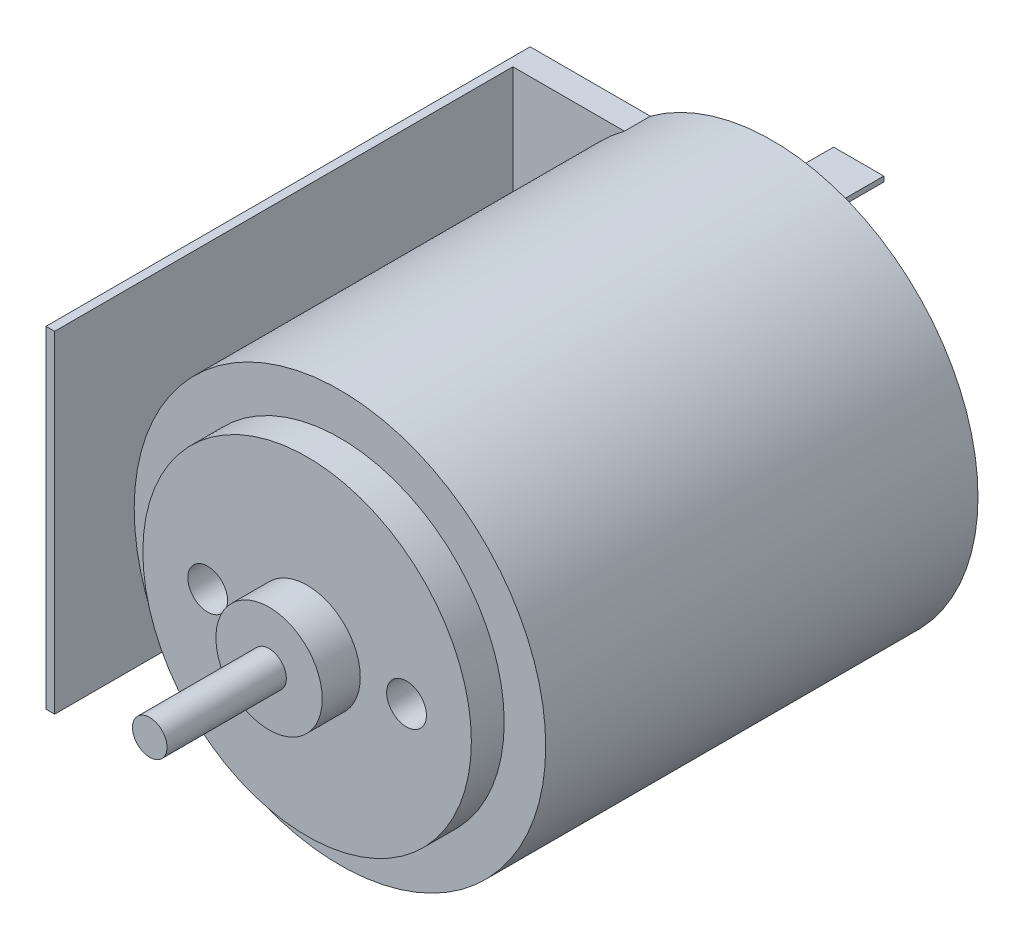
SolidWorks part; units mm, degrees
ref_plane "正面" through (0, 0, 0) normal (0, 0, 1) x (1, 0, 0)
ref_plane "平面" through (0, 0, 0) normal (0, 1, 0) x (1, 0, 0)
ref_plane "右側面" through (0, 0, 0) normal (1, 0, 0) x (0, 0, -1)
sketch "ｽｹｯﾁ2" plane through (0, 0, 0) normal (0, 0, 1) x (1, 0, 0)
  circle A0 centre (0, 0) radius 9.5
  circle A1 centre (0, 0) radius 11.9
  circle A2 centre (0, 0) radius 3.075
  circle A3 centre (0, 0) radius 1
  circle A4 centre (0, 0) radius 4.25
  dimension "D1" = 23.8
  dimension "D2" = 19
  dimension "D3" = 6.15
  dimension "D4" = 2
  dimension "D5" = 8.5
extrude "ﾎﾞｽ - 押し出し1" add sketch "ｽｹｯﾁ2" along normal blind 36 contours A3 region at (0, 0, 0)
extrude "ﾎﾞｽ - 押し出し2" add sketch "ｽｹｯﾁ2<4>" along normal blind 29.1 contours A2 A3 region at (-2.988, 0, 0)
sketch "ｽｹｯﾁ2<4>" plane through (0, 0, 0) normal (0, 0, 1) x (1, 0, 0) same geometry as "ｽｹｯﾁ2"
extrude "ﾎﾞｽ - 押し出し3" add sketch "ｽｹｯﾁ2<5>" along normal blind 26.9 and the other way blind 2 contours A4 A2 region at (-4.1298, 0, 0)
sketch "ｽｹｯﾁ2<5>" plane through (0, 0, 0) normal (0, 0, 1) x (1, 0, 0) same geometry as "ｽｹｯﾁ2"
extrude "ﾎﾞｽ - 押し出し4" add sketch "ｽｹｯﾁ2<6>" along normal blind 26.9 contours A0 A4 region at (-9.2313, 0, 0)
sketch "ｽｹｯﾁ2<6>" plane through (0, 0, 0) normal (0, 0, 1) x (1, 0, 0) same geometry as "ｽｹｯﾁ2"
extrude "ﾎﾞｽ - 押し出し5" add sketch "ｽｹｯﾁ2<7>" along normal blind 25 contours A1 A0 region at (-11.5634, 0, 0)
sketch "ｽｹｯﾁ2<7>" plane through (0, 0, 0) normal (0, 0, 1) x (1, 0, 0) same geometry as "ｽｹｯﾁ2"
ref_plane "平面1" through (0, 0, 26.9) normal (0, 0, 1) x (1, 0, 0)
ref_plane "平面2" through (0, 0, -10) normal (0, 0, -1) x (-1, 0, 0)
ref_plane "平面3" through (0, 0, 0) normal (0, 0, -1) x (-1, 0, 0)
sketch "ｽｹｯﾁ5" plane through (0, 0, 0) normal (0, 0, -1) x (-1, 0, 0)
  line L5 (1.45, -7.8068) -> (-1.45, -7.8068)
  line L6 (1.45, -7.8068) -> (1.45, -7.5068)
  line L11 (1.45, -7.5068) -> (-1.45, -7.5068)
  line L12 (-1.45, -7.8068) -> (-1.45, -7.5068)
  line L13 (1.45, -7.8068) -> (-1.45, -7.5068) construction
  line L14 (1.45, -7.5068) -> (-1.45, -7.8068) construction
  line L15 (-1.45, 8.3397) -> (1.45, 8.3397)
  line L16 (-1.45, 8.3397) -> (-1.45, 8.0397)
  line L17 (-1.45, 8.0397) -> (1.45, 8.0397)
  line L18 (1.45, 8.3397) -> (1.45, 8.0397)
  line L19 (-1.45, 8.3397) -> (1.45, 8.0397) construction
  line L20 (-1.45, 8.0397) -> (1.45, 8.3397) construction
  circle A0 centre (6.45, 0) radius 1
  circle A1 centre (-6.45, 0) radius 1
  point P4 (-0.6526, 8.1897)
  point P5 (0, 8.1897)
  point P6 (0, -7.6568)
  point P9 (1.8202, -7.6568)
  dimension "D3" = 2
  dimension "D4" = 2
  dimension "D1" = 6.45
  dimension "D2" = 6.45
  dimension "D5" = 2.9
  dimension "D6" = 0.3
  dimension "D7" = 2.9
  dimension "D8" = 0.3
extrude "ﾎﾞｽ - 押し出し6" add sketch "ｽｹｯﾁ5" along normal blind 5 contours L16 L15 L18 L17 | L6 L5 L12 L11
sketch "ｽｹｯﾁ6" plane through (0, 0, 0) normal (0, 0, -1) x (-1, 0, 0)
  circle A0 centre (6.45, 0) radius 1
  circle A1 centre (-6.45, 0) radius 1
  dimension "D1" = 6.45
  dimension "D2" = 6.45
hole_wizard "M2 ねじ穴2" positions "ｽｹｯﾁ9" profile "ｽｹｯﾁ10" tap size "M2" standard "IS"
sketch "ｽｹｯﾁ9" plane through (0, 0, 0) normal (0, 0, -1) x (-1, 0, 0)
  point P0 (-6.45, 0)
  point P3 (6.45, 0)
sketch "ｽｹｯﾁ10" plane through (6.45, 0, 0) normal (1, 0, 0) x (0, 1, 0)
  line L0 (0, 0) -> (0, 6.4807)
  line L1 (0, 6.4807) -> (0.8, 6)
  line L2 (0.8, 6) -> (0.8, 0)
  line L5 (0.8, 0) -> (0, 0)
  line L10 (0, 6.4807) -> (-0.8, 6) construction
  line L11 (0, -6.35) -> (0, 107.95) construction
  dimension "ねじ下穴ﾄﾞﾘﾙ直径" = 1.6
  dimension "ねじ下穴ﾄﾞﾘﾙの深さ" = 6
  dimension "ﾄﾞﾘﾙ角度" = 118
cosmetic thread "穴のねじ山2" parameters "D1"=4, "D2"=2
cosmetic thread "穴のねじ山3" parameters "D1"=4, "D2"=2
ref_plane "平面4" through (0, 0, 36.9) normal (0, 0, 1) x (1, 0, 0)
sketch "ｽｹｯﾁ14" plane through (0, 0, 26.9) normal (0, 0, 1) x (1, 0, 0)
  circle A0 centre (5.75, 0) radius 1.15
  circle A1 centre (-5.75, 0) radius 1.15
  dimension "D3" = 2.3
  dimension "D4" = 2.3
  dimension "D1" = 5.75
  dimension "D2" = 5.75
extrude "ｶｯﾄ - 押し出し1" cut sketch "ｽｹｯﾁ14" against normal blind 3
sketch "ｽｹｯﾁ15" plane through (0, 0, 0) normal (0, 0, -1) x (-1, 0, 0)
  line L1 (13.5, -9.589) -> (14, -9.589)
  line L2 (13.5, -9.589) -> (13.5, 9.589)
  line L3 (13.5, 9.589) -> (14, 9.589)
  line L4 (14, -9.589) -> (14, 9.589)
  line L5 (13.5, -9.589) -> (14, 9.589) construction
  line L6 (13.5, 9.589) -> (14, -9.589) construction
  point P0 (13.75, 0)
  dimension "D1" = 13.5
  dimension "D2" = 0.5
extrude "ﾎﾞｽ - 押し出し7" add sketch "ｽｹｯﾁ15" against normal blind 28 separate body
ref_plane "平面5" through (-24, 0, 0) normal (-1, 0, 0) x (0, 0, 1)
sketch "ｽｹｯﾁ16" plane through (-24, 0, 0) normal (-1, 0, 0) x (0, 0, 1)
  line L0 (0, 9.589) -> (0, -9.4889)
  line L1 (0, 13.09) -> (0, -13.09) construction
  line L2 (28, 9.589) -> (0, 9.589) construction
  line L3 (0, -9.4889) -> (1.5, -9.589)
  line L4 (28, -9.589) -> (0, -9.589) construction
  line L5 (1.5, -9.589) -> (1.5, 9.589)
  line L6 (1.5, 9.589) -> (0, 9.589)
  dimension "D1" = 1.5
ref_plane "平面6" through (-14, 0, 0) normal (-1, 0, 0) x (0, 0, 1)
sketch "ｽｹｯﾁ17" plane through (-14, 0, 0) normal (-1, 0, 0) x (0, 0, 1)
  line L0 (0, 9.589) -> (0, -9.589)
  line L1 (0, -9.589) -> (1.5, -9.589)
  line L2 (28, -9.589) -> (0, -9.589) construction
  line L3 (1.5, -9.589) -> (1.5, 9.589)
  line L4 (28, 9.589) -> (0, 9.589) construction
  line L5 (1.5, 9.589) -> (0, 9.589)
  dimension "D1" = 1.5
extrude "ﾎﾞｽ - 押し出し9" add sketch "ｽｹｯﾁ17" against normal blind 10
